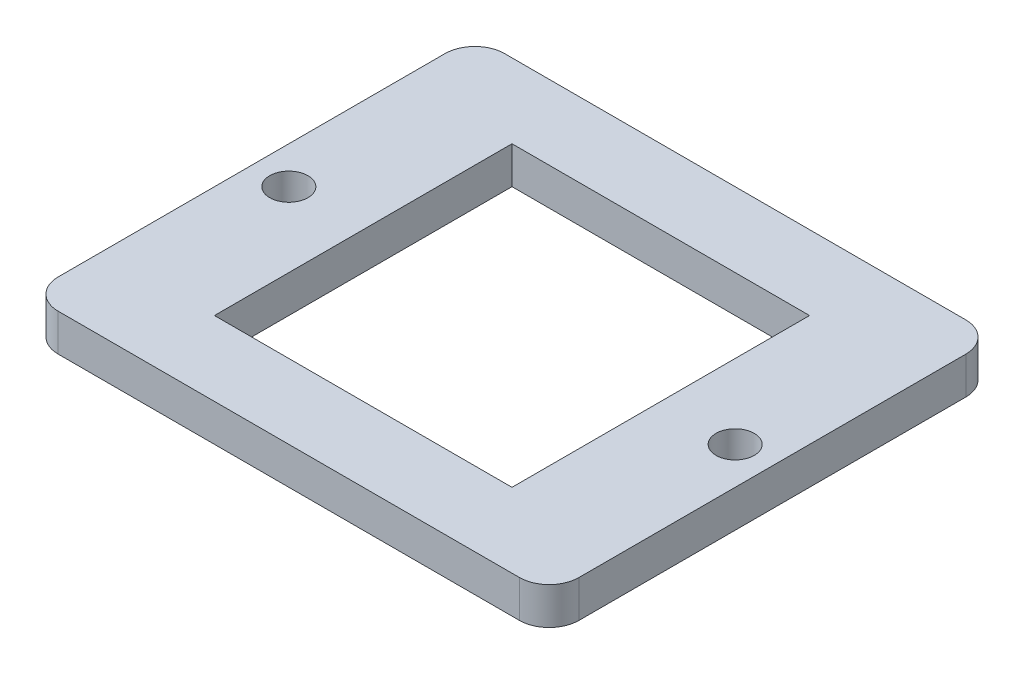
SolidWorks part; units mm, degrees
ref_plane "Front Plane" through (0, 0, 0) normal (0, 0, 1) x (1, 0, 0)
ref_plane "Top Plane" through (0, 0, 0) normal (0, 1, 0) x (1, 0, 0)
ref_plane "Right Plane" through (0, 0, 0) normal (1, 0, 0) x (0, 0, -1)
sketch "Sketch1" plane through (0, 0, 0) normal (0, 1, 0) x (1, 0, 0)
  line L1 (-22.225, 19.05) -> (22.225, 19.05)
  line L2 (-22.225, 19.05) -> (-22.225, -19.05)
  line L3 (-22.225, -19.05) -> (22.225, -19.05)
  line L4 (22.225, 19.05) -> (22.225, -19.05)
  line L5 (-22.225, 19.05) -> (22.225, -19.05) construction
  line L6 (-22.225, -19.05) -> (22.225, 19.05) construction
  point P0 (0, 0)
  dimension "D1" = 44.45
  dimension "D2" = 38.1
extrude "Boss-Extrude1" add sketch "Sketch1" along normal blind 3.175
sketch "Sketch2" plane through (0, 3.175, 0) normal (0, 1, 0) x (1, 0, 0)
  line L1 (-12.7, 12.7) -> (12.7, 12.7)
  line L2 (-12.7, 12.7) -> (-12.7, -12.7)
  line L3 (-12.7, -12.7) -> (12.7, -12.7)
  line L4 (12.7, 12.7) -> (12.7, -12.7)
  line L5 (-12.7, 12.7) -> (12.7, -12.7) construction
  line L6 (-12.7, -12.7) -> (12.7, 12.7) construction
  point P0 (0, 0)
  dimension "D1" = 25.4
  dimension "D2" = 25.4
extrude "Cut-Extrude1" cut sketch "Sketch2" against normal blind 3.175
hole_wizard "#4 Clearance Hole1" positions "Sketch4" profile "Sketch3" hole size "#4" standard "ANSI Inch"
sketch "Sketch4" plane through (0, 3.175, 0) normal (0, 1, 0) x (1, 0, 0)
  line L0 (-12.7, 12.7) -> (-12.7, -12.7) construction
  line L1 (12.7, -12.7) -> (12.7, 12.7) construction
  line L2 (12.7, 12.7) -> (-12.7, 12.7) construction
  point P0 (-19.05, 0)
  point P2 (19.05, 0)
  point P9 (12.7, 0)
  dimension "D1" = 6.35
  dimension "D2" = 6.35
  dimension "D3" = 12.7
  dimension "D4" = 12.7
sketch "Sketch3" plane through (-19.05, 3.175, 0) normal (1, 0, 0) x (0, 0, 1)
  line L0 (0, 0) -> (0, 11.1406)
  line L1 (0, 11.1406) -> (1.6319, 10.16)
  line L2 (1.6319, 10.16) -> (1.6319, 0)
  line L5 (1.6319, 0) -> (0, 0)
  line L10 (0, 11.1406) -> (-1.6319, 10.16) construction
  line L11 (0, -6.35) -> (0, 107.95) construction
  dimension "Hole Dia." = 3.2639
  dimension "Hole Depth" = 10.16
  dimension "Drill Angle" = 118
fillet "Fillet1" radius 2.54 4 edges at (22.225, 1.5875, 19.05) (22.225, 1.5875, -19.05) (-22.225, 1.5875, -19.05) (-22.225, 1.5875, 19.05)
